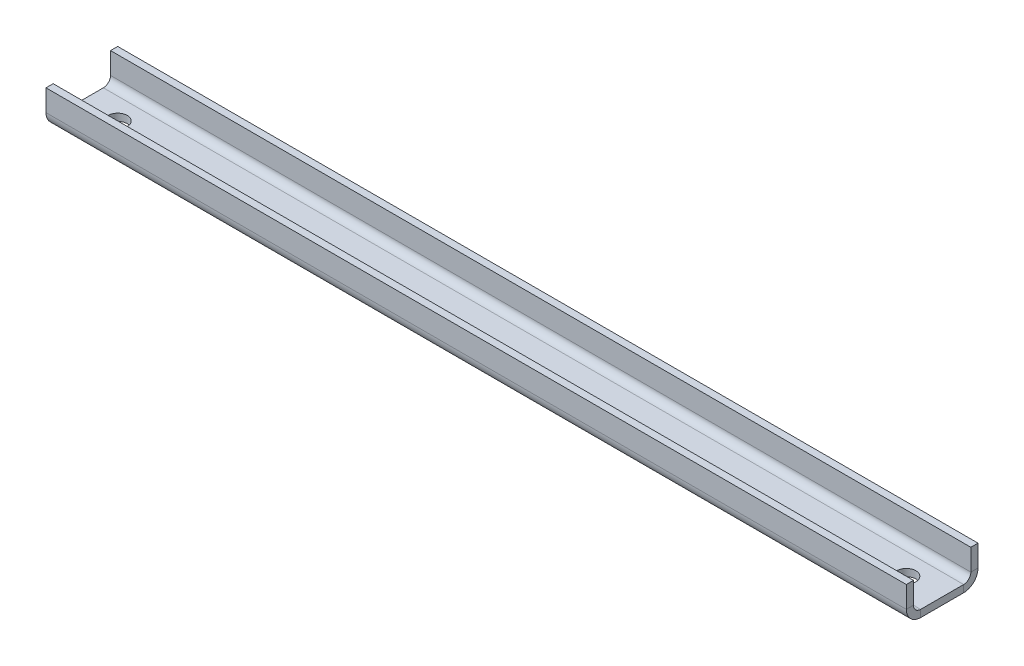
SolidWorks part; units mm, degrees
note: The reader was unsure of these and kept them because the rebuilt part matched: flange length of "Tôle pliée sur arête1".
ref_plane "Plan de face" through (0, 0, 0) normal (0, 0, 1) x (1, 0, 0)
ref_plane "Plan de dessus" through (0, 0, 0) normal (0, 1, 0) x (1, 0, 0)
ref_plane "Plan de droite" through (0, 0, 0) normal (1, 0, 0) x (0, 0, -1)
sketch "Esquisse2" plane through (0, 0, 0) normal (0, 1, 0) x (1, 0, 0)
  line L1 (0, 0) -> (360, 0)
  line L2 (0, 0) -> (0, 30)
  line L3 (0, 30) -> (360, 30)
  line L4 (360, 0) -> (360, 30)
  dimension "D1" = 30
  dimension "D2" = 360
sheet metal parameters "Tôlerie 1" thickness 3 parameters "D1"=3
base flange "Tôle de base pliée1" sketch "Esquisse2" thickness 3 reverse thickness direction no parameters "D1"=3
edge flange "Tôle pliée sur arête1" sketch "Esquisse7" flange profiles "Esquisse7", "Esquisse9" flange angle 90 flange length 15 flange position material inside bend radius 3 thickness 3 relief rectangular parameters "D6"=10, "D8"=1
sketch "Esquisse7" plane through (0, 0, 0) normal (0, 0, 1) x (1, 0, 0)
  line L0 (0, 0) -> (360, 0) construction
  line L1 (0, 0) -> (360, 0)
  line L2 (0, 0) -> (0, 12)
  line L3 (0, 12) -> (360, 12)
  line L4 (360, 12) -> (360, 0)
sketch "Esquisse9" plane through (0, 0, -30) normal (0, 0, -1) x (-1, 0, 0)
  line L0 (-360, 0) -> (0, 0) construction
  line L1 (-360, 0) -> (0, 0)
  line L2 (-360, 0) -> (-360, 12)
  line L3 (-360, 12) -> (0, 12)
  line L4 (0, 12) -> (0, 0)
bend "Pli d'arête1" bend radius 3 bend angle 90 parameters "D5"=1
bend "Pli d'arête2" bend radius 3 bend angle 90 parameters "D5"=2
sketch "Esquisse10" plane through (0, 0, 0) normal (0, 1, 0) x (1, 0, 0)
  circle A0 centre (15, 15) radius 4
  circle A1 centre (345, 15) radius 4
  dimension "D1" = 15
  dimension "D2" = 330
extrude "Enlèv. mat.-Extru.1" cut sketch "Esquisse10" against normal up to next normal cut yes
flat pattern "Etat déplié1" [suppressed]
sketch "Lignes de pliage1" plane through (0, 0, 0) normal (0, 1, 0) x (1, 0, 0)
sketch3d "Cube de visualisation1" [suppressed]
  line L0 (-650, 50, 0) -> (0, 50, 0) construction
  line L1 (-650, 0, 0) -> (0, 0, 0) construction
  line L2 (-650, 50, 0) -> (-650, 0, 0) construction
  line L3 (0, 50, 0) -> (0, 0, 0) construction
bend of the flat pattern "Dépliage-<Pli d'arête1>1"
bend of the flat pattern "Dépliage-<Pli d'arête2>1"
